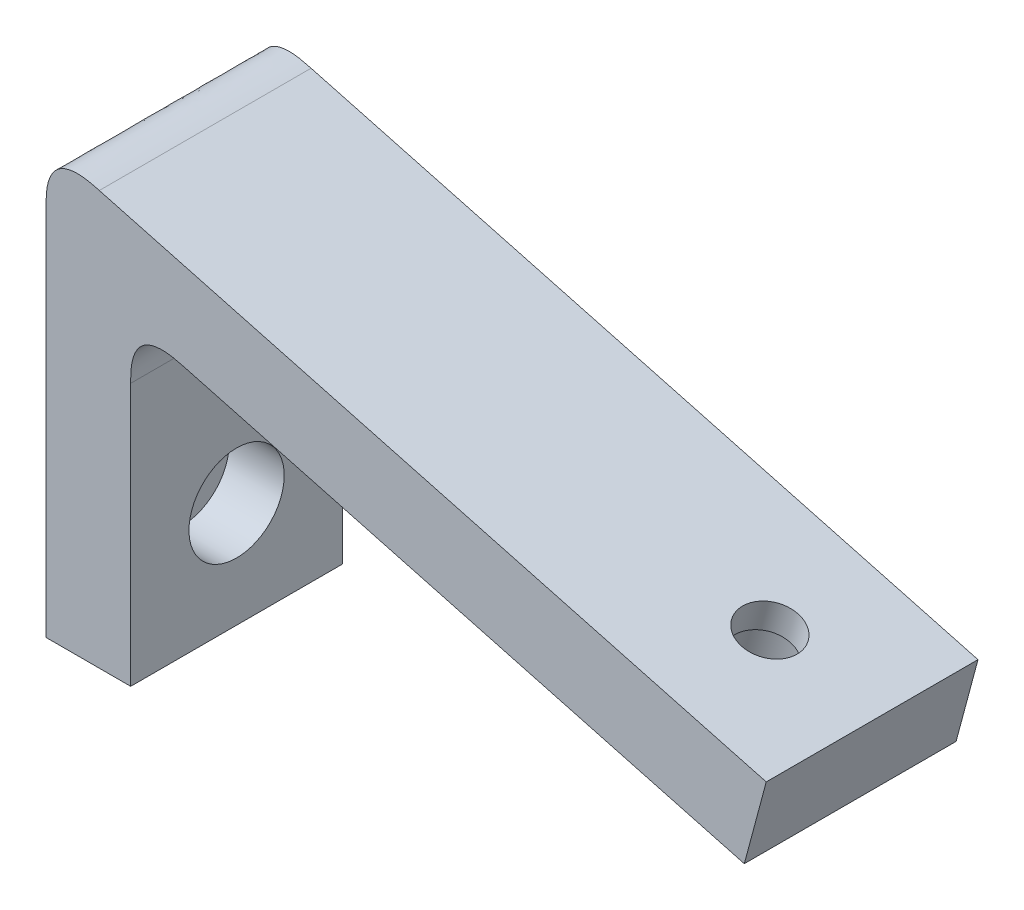
SolidWorks part; units mm, degrees
ref_plane "Front Plane" through (0, 0, 0) normal (0, 0, 1) x (1, 0, 0)
ref_plane "Top Plane" through (0, 0, 0) normal (0, 1, 0) x (1, 0, 0)
ref_plane "Right Plane" through (0, 0, 0) normal (1, 0, 0) x (0, 0, -1)
sketch "Sketch1" plane through (0, 0, 0) normal (0, 0, 1) x (1, 0, 0)
  line L0 (0, 0) -> (0, 51.3408)
  line L1 (0, 51.3408) -> (86.3931, 28.1918)
  line L2 (86.3931, 28.1918) -> (83.7635, 18.378)
  line L3 (83.7635, 18.378) -> (10.16, 38.1)
  line L4 (10.16, 38.1) -> (10.16, 0)
  line L5 (10.16, 0) -> (0, 0)
  dimension "D1" = 38.1
  dimension "D2" = 76.2
  dimension "D3" = 75
  dimension "D4" = 10.16
  dimension "D5" = 10.16
extrude "Boss-Extrude1" add sketch "Sketch1" along normal blind 25.4 contours L5 L4 L3 L2 L1 L0 region at (1.005, 25.6704, 0)
sketch "Sketch2" plane through (0, 0, 0) normal (-1, 0, 0) x (0, 0, 1)
  line L0 (0, 12.7) -> (25.4, 12.7) construction
  line L1 (0, 0) -> (0, 51.3408) construction
  line L2 (25.4, 0) -> (25.4, 51.3408) construction
  line L3 (25.4, 0) -> (0, 0) construction
  point P6 (12.7, 12.7)
  dimension "D1" = 12.7
sketch "Sketch3" plane through (12.8352, 47.9016, 0) normal (0.2588, 0.9659, 0) x (0.9659, -0.2588, 0)
  line L0 (63.4528, 0) -> (63.4528, -25.4) construction
  line L1 (-13.288, 0) -> (76.1528, 0) construction
  line L2 (-13.288, -25.4) -> (76.1528, -25.4) construction
  line L3 (76.1528, -25.4) -> (76.1528, 0) construction
  point P6 (63.4528, -12.7)
  dimension "D1" = 12.7
hole_wizard "1/4 Clearance Hole1" positions "Sketch4" profile "Sketch5" hole size "1/4" standard "ANSI Inch"
sketch "Sketch4" plane through (0, 0, 0) normal (-1, 0, 0) x (0, 0, 1)
  point P0 (12.7, 12.7)
sketch "Sketch5" plane through (0, 12.7, 12.7) normal (0, 1, 0) x (0, 0, 1)
  line L0 (0, 0) -> (0, 12.1898)
  line L1 (0, 12.1898) -> (3.3782, 10.16)
  line L2 (3.3782, 10.16) -> (3.3782, 0)
  line L5 (3.3782, 0) -> (0, 0)
  line L10 (0, 12.1898) -> (-3.3782, 10.16) construction
  line L11 (0, -6.35) -> (0, 107.95) construction
  dimension "Hole Dia." = 6.7564
  dimension "Hole Depth" = 10.16
  dimension "Drill Angle" = 118
hole_wizard "1/4 Clearance Hole2" positions "Sketch6" profile "Sketch7" hole size "1/4" standard "ANSI Inch"
sketch "Sketch6" plane through (12.8352, 47.9016, 0) normal (0.2588, 0.9659, 0) x (0.9659, -0.2588, 0)
  point P0 (63.4528, -12.7)
sketch "Sketch7" plane through (74.1259, 31.4788, 12.7) normal (0, 0, 1) x (-0.9659, 0.2588, 0)
  line L0 (0, 0) -> (0, 12.1898)
  line L1 (0, 12.1898) -> (3.3782, 10.16)
  line L2 (3.3782, 10.16) -> (3.3782, 0)
  line L5 (3.3782, 0) -> (0, 0)
  line L10 (0, 12.1898) -> (-3.3782, 10.16) construction
  line L11 (0, -6.35) -> (0, 107.95) construction
  dimension "Hole Dia." = 6.7564
  dimension "Hole Depth" = 10.16
  dimension "Drill Angle" = 118
fillet "Fillet1" radius 5.08 2 edges at (10.16, 38.1, 12.7) (0, 51.3408, 12.7) curvature continuous yes
sketch "Sketch8" plane through (10.2056, 38.0878, 0) normal (-0.2588, -0.9659, 0) x (0.9659, -0.2588, 0)
  circle A0 centre (63.4528, 12.7) radius 5.715
  dimension "D1" = 11.43
extrude "Cut-Extrude1" cut sketch "Sketch8" against normal blind 6.604
sketch "Sketch9" plane through (10.16, 0, 0) normal (1, 0, 0) x (0, 0, -1)
  line L0 (0, 12.7) -> (-25.4, 12.7) construction
  circle A0 centre (-12.7, 12.7) radius 5.715
  dimension "D1" = 11.43
extrude "Cut-Extrude2" cut sketch "Sketch9" against normal blind 6.604
